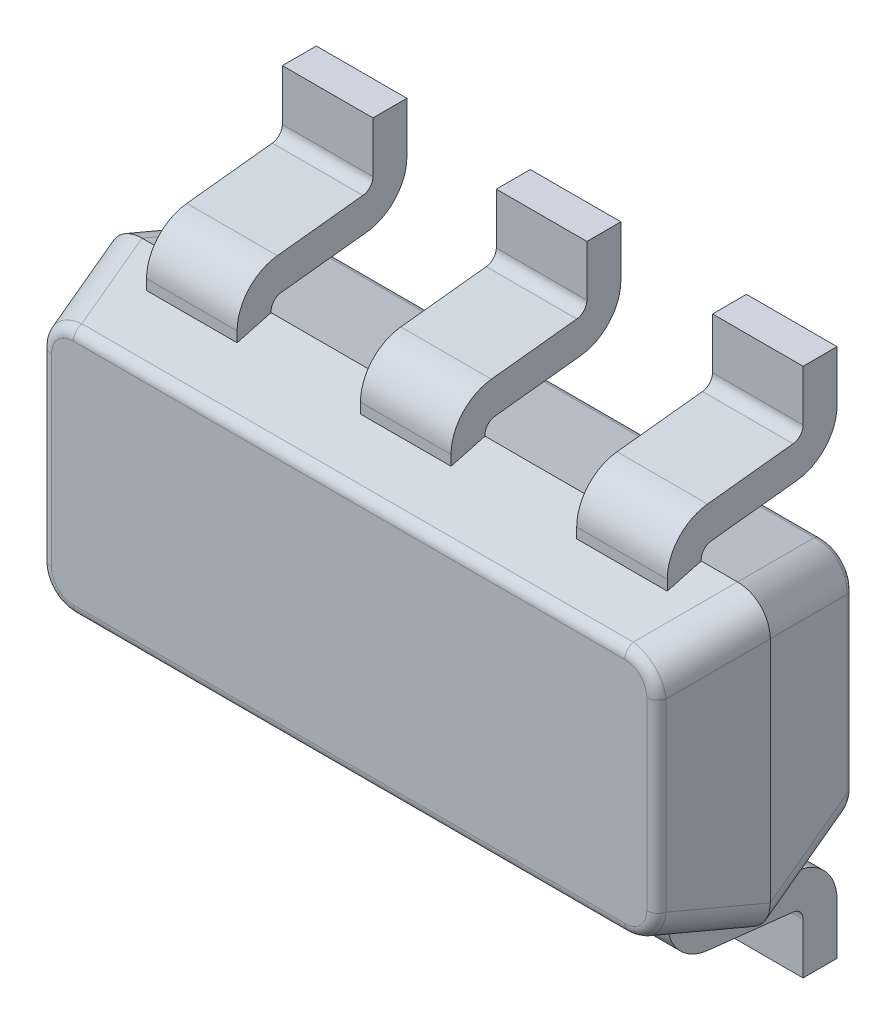
SolidWorks part; units mm, degrees
note: The reader was unsure of these and kept them because the rebuilt part matched: shared geometry of "Эскиз2<3>".
ref_plane "Спереди" through (0, 0, 0) normal (0, 0, 1) x (1, 0, 0)
ref_plane "Сверху" through (0, 0, 0) normal (0, 1, 0) x (1, 0, 0)
ref_plane "Справа" through (0, 0, 0) normal (1, 0, 0) x (0, 0, -1)
sketch "Эскиз1" plane through (0, 0, 0) normal (0, 0, 1) x (1, 0, 0)
  line L1 (-1.46, 0.65) -> (1.46, 0.65)
  line L2 (-1.46, 0.65) -> (-1.46, -0.65)
  line L3 (-1.46, -0.65) -> (1.46, -0.65)
  line L4 (1.46, 0.65) -> (1.46, -0.65)
  point P0 (0, 0)
extrude "Вытянуть1" add sketch "Эскиз1" along normal blind 0.4 draft 15 and the other way blind 0.5 draft 15 from offset 0.6
sketch "Эскиз2" plane through (0, 0, 0) normal (1, 0, 0) x (0, 0, -1)
  line L0 (0, -1.17) -> (0, -0.9453)
  line L1 (0, -1.17) -> (-0.15, -1.17)
  line L2 (-0.6, -0.6552) -> (-0.6, -0.6)
  line L3 (-0.6, 0.65) -> (-0.6, -0.65) construction
  line L4 (-0.75, -0.6) -> (-0.6, -0.6)
  line L5 (-0.15, -1.17) -> (-0.15, -0.9453)
  line L7 (-0.5555, -0.7049) -> (-0.1781, -0.7465)
  line L8 (-0.75, -0.6552) -> (-0.75, -0.6)
  line L9 (-0.036, 0) -> (-1.0524, 0) construction
  line L10 (-0.1945, 0.8956) -> (-0.5719, 0.854)
  line L11 (-0.1945, -0.8956) -> (-0.5719, -0.854)
  line L12 (-0.75, 0.6552) -> (-0.75, 0.6)
  line L13 (-0.5555, 0.7049) -> (-0.1781, 0.7465)
  line L14 (-0.15, 1.17) -> (-0.15, 0.9453)
  line L15 (-0.75, 0.6) -> (-0.6, 0.6)
  line L16 (-0.6, 0.6552) -> (-0.6, 0.6)
  line L17 (0, 1.17) -> (-0.15, 1.17)
  line L18 (0, 1.17) -> (0, 0.9453)
  arc A0 (-0.6, -0.6552) -> (-0.5555, -0.7049) centre (-0.55, -0.6552) ccw
  arc A1 (-0.15, -0.9453) -> (-0.1945, -0.8956) centre (-0.2, -0.9453) ccw
  arc A2 (-0.1781, -0.7465) -> (0, -0.9453) centre (-0.2, -0.9453) cw
  arc A3 (-0.5719, -0.854) -> (-0.75, -0.6552) centre (-0.55, -0.6552) cw
  arc A4 (-0.5719, 0.854) -> (-0.75, 0.6552) centre (-0.55, 0.6552) ccw
  arc A5 (-0.1781, 0.7465) -> (0, 0.9453) centre (-0.2, 0.9453) ccw
  arc A6 (-0.15, 0.9453) -> (-0.1945, 0.8956) centre (-0.2, 0.9453) cw
  arc A7 (-0.6, 0.6552) -> (-0.5555, 0.7049) centre (-0.55, 0.6552) cw
extrude "Вытянуть2" add sketch "Эскиз2" along normal blind 0.2 and the other way blind 0.2 from offset 0.955
pattern_linear "Линейный массив1" count 2 spacing 1.9 along (-1, 0, 0) of "Вытянуть2"
extrude "Вытянуть3" add sketch "Эскиз2<3>" along normal blind 0.2 and the other way blind 0.2 contours L18 A5 L13 A7 L16 L15 L12 A4 L10 A6 L14 L17
sketch "Эскиз2<3>" plane through (0, 0, 0) normal (1, 0, 0) x (0, 0, -1) same geometry as "Эскиз2"
fillet "Скругление1" radius 0.15 8 edges at (1.4064, -0.5964, 0.8) (1.4064, 0.5964, 0.8) (-1.4064, 0.5964, 0.8) (-1.4064, -0.5964, 0.8) (1.393, -0.583, 0.35) (-1.393, -0.583, 0.35) (-1.393, 0.583, 0.35) (1.393, 0.583, 0.35)
fillet "Скругление2" radius 0.05 16 edges at (-1.311, -0.501, 1) (-1.3528, 0, 1) (-1.311, 0.501, 1) (0, 0.5428, 1) (1.311, 0.501, 1) (1.3528, 0, 1) (1.311, -0.501, 1) (0, -0.5428, 1) (1.2842, -0.4742, 0.1) (1.326, 0, 0.1) (1.2842, 0.4742, 0.1) (0, 0.516, 0.1) (-1.2842, 0.4742, 0.1) (-1.326, 0, 0.1) (-1.2842, -0.4742, 0.1) (0, -0.516, 0.1)
